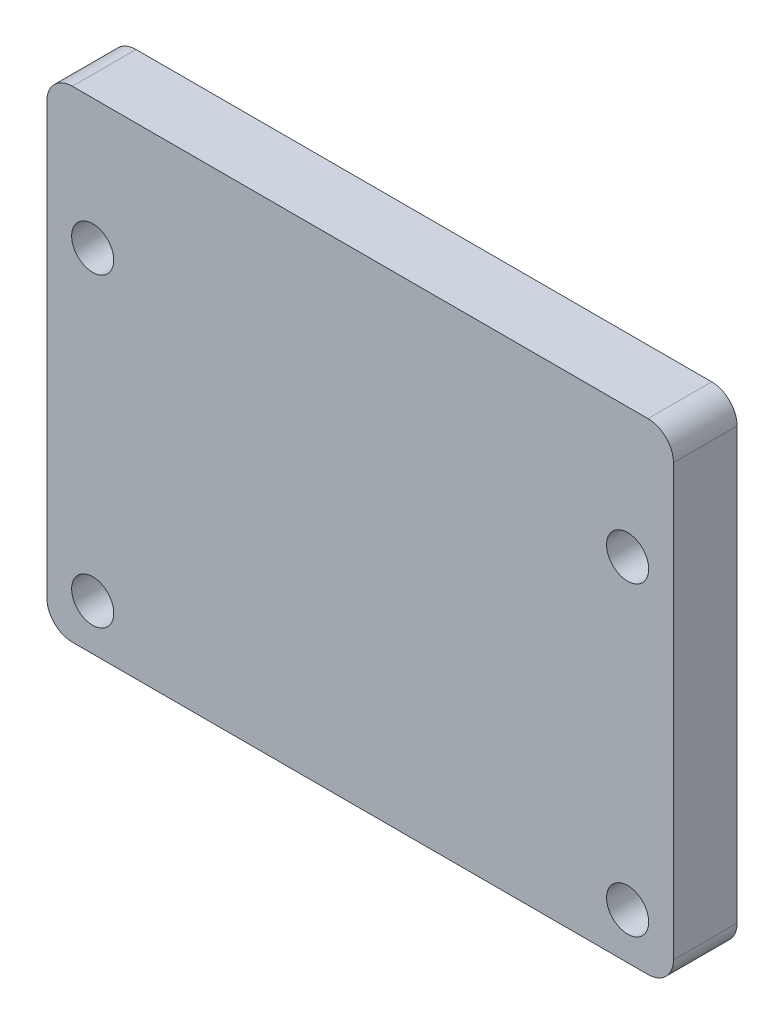
SolidWorks part; units mm, degrees
material "ABS"
ref_plane "X-Y Datum" through (0, 0, 0) normal (0, 0, 1) x (1, 0, 0)
ref_plane "X-Z Datum" through (0, 0, 0) normal (0, 1, 0) x (1, 0, 0)
ref_plane "Y-Z Datum" through (0, 0, 0) normal (1, 0, 0) x (0, 0, -1)
sketch "Sketch1" plane through (0, 0, 6.35) normal (0, 0, -1) x (-1, 0, 0)
  line L3 (-31.242, -24.003) -> (31.242, -24.003)
  line L4 (-31.242, -24.003) -> (-31.242, 24.003)
  line L5 (-31.242, 24.003) -> (31.242, 24.003)
  line L6 (31.242, -24.003) -> (31.242, 24.003)
  line L7 (-31.242, -24.003) -> (31.242, 24.003) construction
  line L8 (-31.242, 24.003) -> (31.242, -24.003) construction
  circle A0 centre (-26.67, -19.431) radius 2.1 construction
  circle A1 centre (26.67, -19.431) radius 2.1 construction
  circle A2 centre (26.67, 11.049) radius 2.1 construction
  circle A3 centre (-26.67, 11.049) radius 2.1 construction
  circle A4 centre (-26.67, -19.431) radius 2.1
  circle A5 centre (26.67, -19.431) radius 2.1
  circle A6 centre (26.67, 11.049) radius 2.1
  circle A7 centre (-26.67, 11.049) radius 2.1
  point P4 (0, 0)
  dimension "D3" = 62.484
  dimension "D4" = 48.006
extrude "Boss-Extrude1" add sketch "Sketch1" along normal blind 6.35
fillet "Fillet1" radius 2.54 4 edges at (-31.242, 24.003, 3.175) (-31.242, -24.003, 3.175) (31.242, -24.003, 3.175) (31.242, 24.003, 3.175)
